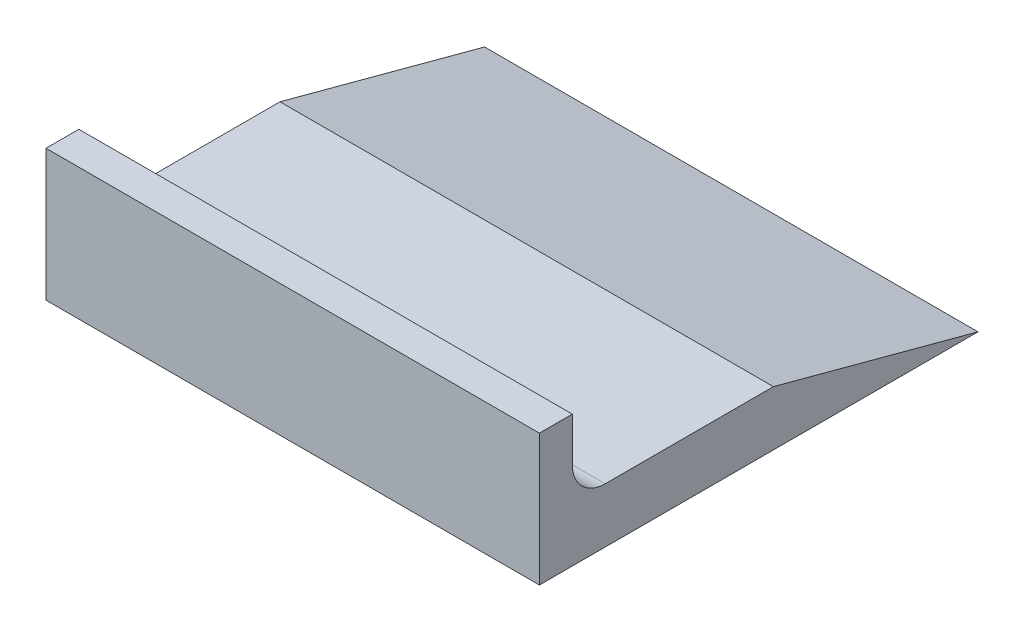
SolidWorks part; units mm, degrees
ref_plane "Спереди" through (0, 0, 0) normal (0, 0, 1) x (1, 0, 0)
ref_plane "Сверху" through (0, 0, 0) normal (0, 1, 0) x (1, 0, 0)
ref_plane "Справа" through (0, 0, 0) normal (1, 0, 0) x (0, 0, -1)
sketch "Sketch1" plane through (0, 0, 0) normal (0, 1, 0) x (1, 0, 0)
  line L1 (-22.5, 20) -> (22.5, 20)
  line L2 (-22.5, 20) -> (-22.5, -20)
  line L3 (-22.5, -20) -> (22.5, -20)
  line L4 (22.5, 20) -> (22.5, -20)
  line L5 (-22.5, 20) -> (22.5, -20) construction
  line L6 (-22.5, -20) -> (22.5, 20) construction
  point P0 (0, 0)
extrude "Boss-Extrude1" add sketch "Sketch1" along normal blind 5
chamfer "Chamfer1" distance 5 angle 75 1 edges at (0, 5, -20) first distance on face at (0, 2.5, -20)
sketch "Sketch2" plane through (0, 5, 0) normal (0, 1, 0) x (1, 0, 0)
  line L0 (22.5, -20) -> (22.5, 1.3397) construction
  line L1 (-22.5, -20) -> (22.5, -20)
  line L2 (-22.5, -20) -> (-22.5, -17)
  line L3 (-22.5, -17) -> (22.5, -17)
  line L4 (22.5, -20) -> (22.5, -17)
extrude "Boss-Extrude2" add sketch "Sketch2" along normal blind 7
fillet "Fillet1" radius 3 1 edges at (0, 5, 17)
